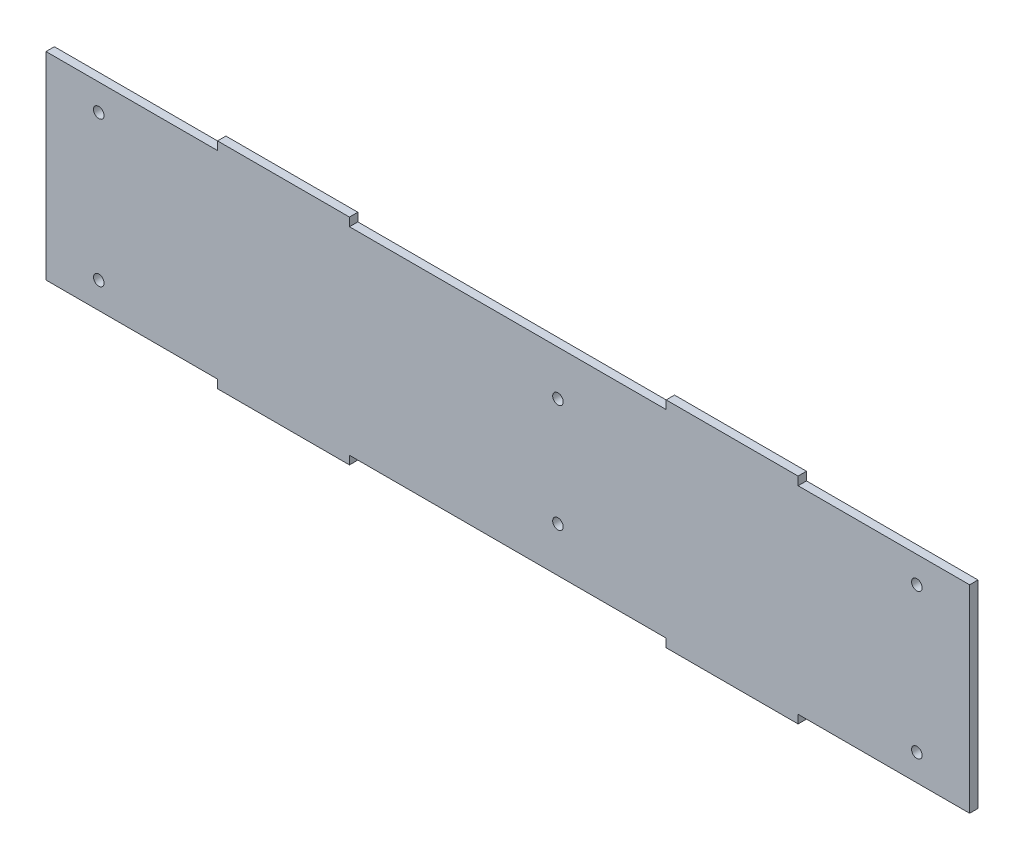
SolidWorks part; units mm, degrees
ref_plane "Front Plane" through (0, 0, 0) normal (0, 0, 1) x (1, 0, 0)
ref_plane "Top Plane" through (0, 0, 0) normal (0, 1, 0) x (1, 0, 0)
ref_plane "Right Plane" through (0, 0, 0) normal (1, 0, 0) x (0, 0, -1)
sketch "Sketch2" plane through (0, 0, 0) normal (0, 0, 1) x (1, 0, 0)
  line L0 (0, 0) -> (65, 0)
  line L1 (0, 0) -> (350, 0) construction
  line L2 (0, 0) -> (0, 75) construction
  line L3 (0, 75) -> (350, 75) construction
  line L4 (350, 0) -> (350, 75) construction
  line L5 (65, 0) -> (65, -3.175)
  line L6 (65, -3.175) -> (115, -3.175)
  line L7 (115, -3.175) -> (115, 0)
  line L8 (115, 0) -> (235, 0)
  line L9 (235, 0) -> (235, -3.175)
  line L10 (235, -3.175) -> (285, -3.175)
  line L11 (285, -3.175) -> (285, 0)
  line L12 (285, 0) -> (350, 0)
  line L13 (350, 0) -> (350, 75)
  line L14 (350, 75) -> (285, 75)
  line L15 (285, 75) -> (285, 78.175)
  line L16 (285, 78.175) -> (235, 78.175)
  line L17 (235, 78.175) -> (235, 75)
  line L18 (235, 75) -> (115, 75)
  line L19 (115, 75) -> (115, 78.175)
  line L20 (115, 78.175) -> (65, 78.175)
  line L21 (65, 78.175) -> (65, 75)
  line L22 (65, 75) -> (0, 75)
  line L23 (0, 75) -> (0, 0)
  circle A0 centre (20, 10) radius 2
  circle A1 centre (330, 10) radius 2
  circle A2 centre (330, 65) radius 2
  circle A3 centre (20, 65) radius 2
  circle A4 centre (194, 17) radius 2
  circle A5 centre (194, 58) radius 2
  dimension "D6" = 4
  dimension "D1" = 3.175
  dimension "D2" = 75
  dimension "D3" = 350
  dimension "D4" = 50
  dimension "D5" = 65
extrude "Boss-Extrude1" add sketch "Sketch2" along normal blind 3.175
